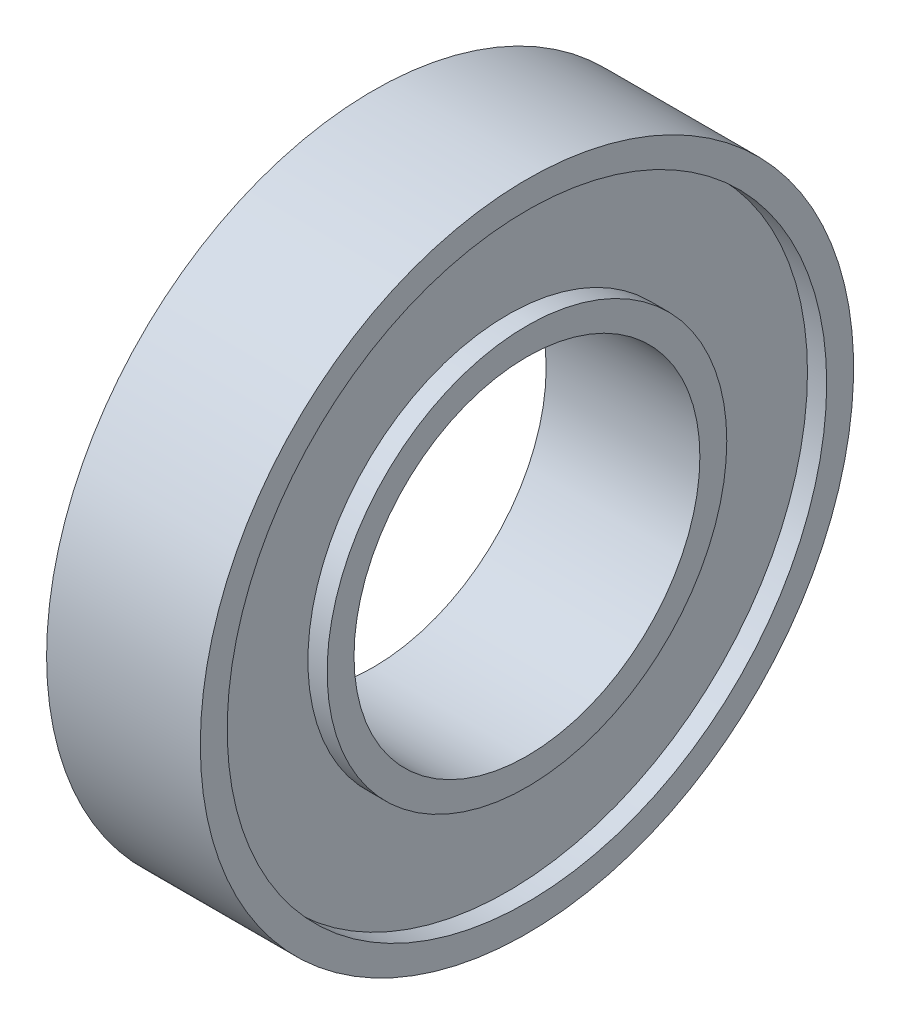
SolidWorks part; units mm, degrees
ref_plane "Alzado" through (0, 0, 0) normal (0, 0, 1) x (1, 0, 0)
ref_plane "Planta" through (0, 0, 0) normal (0, 1, 0) x (1, 0, 0)
ref_plane "Vista lateral" through (0, 0, 0) normal (1, 0, 0) x (0, 0, -1)
sketch "Croquis1" plane through (0, 0, 0) normal (0, 0, 1) x (1, 0, 0)
  line L0 (0, 0) -> (17.4242, 0) construction
  line L1 (0, 0) -> (0, 8.5) construction
  line L2 (0, 8.5) -> (4, 8.5)
  line L3 (4, 8.5) -> (4, 0) construction
  line L4 (0, 4.5) -> (4, 4.5)
  line L5 (0, 4.5) -> (0, 8.5)
  line L6 (4, 4.5) -> (4, 8.5)
  line L7 (4, 8.5) -> (4.0197, 8.5098)
  dimension "D1" = 4
  dimension "D2" = 17
  dimension "D3" = 9
revolve "Revolución1" add sketch "Croquis1" angle 360 about L0 region at (2, 6.5, 0)
sketch "Croquis2" plane through (4, 0, 0) normal (1, 0, 0) x (0, 0, -1)
  circle A2 centre (0, 0) radius 7.8
  circle A3 centre (0, 0) radius 7.8
  circle A5 centre (0, 0) radius 5.2
  circle A6 centre (0, 0) radius 5.2
  dimension "D1" = 0.7
  dimension "D2" = 0.7
extrude "Cortar-Extruir1" cut sketch "Croquis2" against normal blind 0.5
ref_axis "Eje1" through (4, 0, 0) along (-1, 0, 0)
ref_point "Punto1"
ref_point "Punto2"
ref_plane "Plano1" through (2, 0, 0) normal (1, 0, 0) x (0, 0, -1)
mirror "Simetría1" about plane through (2, 0, 0) normal (1, 0, 0) of "Cortar-Extruir1"
